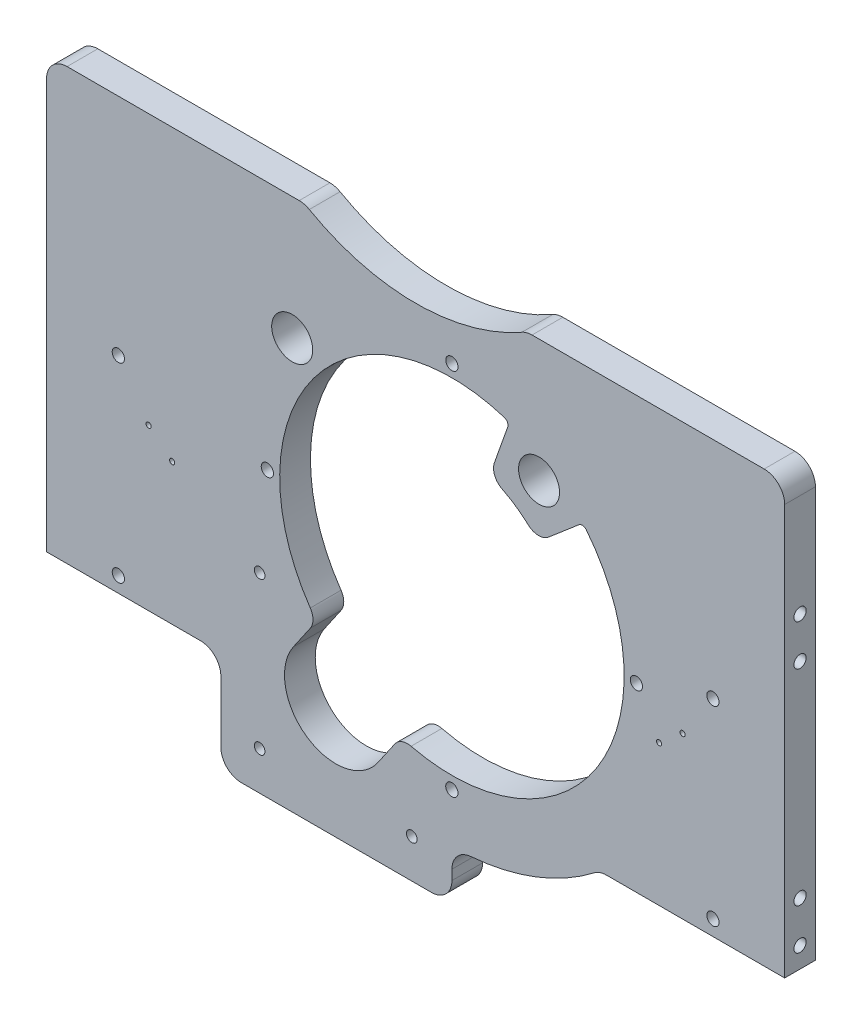
SolidWorks part; units mm, degrees
material "6061 Alloy"
ref_plane "Front Plane" through (0, 0, 0) normal (0, 0, 1) x (1, 0, 0)
ref_plane "Top Plane" through (0, 0, 0) normal (0, 1, 0) x (1, 0, 0)
ref_plane "Right Plane" through (0, 0, 0) normal (1, 0, 0) x (0, 0, -1)
sketch "LayoutSke"
sketch_block_instance "Gearing 2.0-1"
sketch_block "Gearing 2.0" parameters "D5"=76.2, "D6"=25.4, "D7"=101.6, "D8"=19.05, "D1"=228.6, "D2"=123.2, "D3"=85.227, "D4"=76.454, "D9"=39.0329, "D10"=76.454, "D11"=47.625, "D12"=63.5
sketch "Sketch2" plane through (0, 0, 0) normal (0, 0, 1) x (1, 0, 0)
  line L1 (-114.3, 123.2) -> (114.3, 123.2)
  line L2 (-114.3, 123.2) -> (-114.3, -41.9)
  line L3 (-114.3, -41.9) -> (114.3, -41.9)
  line L4 (114.3, 123.2) -> (114.3, -41.9)
  dimension "D1" = 165.1
extrude "Boss-Extrude1" add sketch "Sketch2" along normal blind 9.525
hole_wizard "1/2 (0.5) Diameter Hole1" positions "Sketch3" profile "Sketch4" hole size "1/2" standard "ANSI Inch" end condition through all
sketch "Sketch3" plane through (0, 0, 9.525) normal (0, 0, 1) x (1, 0, 0)
  point P0 (-38.227, 85.227)
  point P3 (38.227, 85.227)
sketch "Sketch4" plane through (-38.227, 85.227, 9.525) normal (1, 0, 0) x (0, -1, 0)
  line L0 (0, 0) -> (0, 9.525)
  line L1 (0, 9.525) -> (6.35, 9.525)
  line L2 (6.35, 9.525) -> (6.35, 0)
  line L5 (6.35, 0) -> (0, 0)
  line L11 (0, -6.35) -> (0, 107.95) construction
  dimension "Thru Hole Dia." = 12.7
  dimension "Thru Hole Depth" = 9.525
ref_axis "MotorShaft" through (-24.7438, -6.3341, 0) along (0, 0, 1)
ref_axis "IntermediateShaft" through (11.2395, 45.9865, 0) along (0, 0, 1)
sketch "Sketch5" plane through (0, 0, 9.525) normal (0, 0, 1) x (1, 0, 0)
  line L0 (11.2395, 45.9865) -> (38.227, 85.227) construction
  line L10 (29.0606, 96.2614) -> (22.9081, 78.9046)
  line L11 (37.8038, 68.6601) -> (51.8105, 80.6153)
  line L12 (11.2395, 45.9865) -> (11.2395, -7.3535) construction
  arc A2 (29.0606, 96.2614) -> (51.8105, 80.6153) centre (11.2395, 45.9865) ccw
  circle A3 centre (11.2395, 45.9865) radius 50.8 construction
  arc A5 (37.8038, 68.6601) -> (22.9081, 78.9046) centre (11.2395, 45.9865) ccw
  dimension "D1" = 2.54
  dimension "D2" = 69.85
  dimension "D3" = 15
  dimension "D4" = 15
extrude "Cut-Extrude2" cut sketch "Sketch5" against normal through all
sketch "Sketch6" plane through (0, 0, 0) normal (0, 0, -1) x (-1, 0, 0)
  line L0 (13.2292, 10.4085) -> (24.7438, -6.3341) construction
  line L1 (26.3093, 19.4043) -> (37.824, 2.6617)
  line L2 (0.149, 1.4126) -> (11.6637, -15.33)
  arc A0 (26.3093, 19.4043) -> (0.149, 1.4126) centre (13.2292, 10.4085) ccw
  arc A1 (11.6637, -15.33) -> (37.824, 2.6617) centre (24.7438, -6.3341) ccw
  arc A2 (-51.8105, 80.6153) -> (-29.0606, 96.2614) centre (-11.2395, 45.9865) ccw construction
  point P4 (18.9865, 2.0372)
  dimension "D1" = 31.75
extrude "Cut-Extrude3" cut sketch "Sketch6" against normal through all
sketch "Sketch7" plane through (0, 0, 0) normal (0, 0, -1) x (-1, 0, 0)
  line L0 (-114.3, 123.2) -> (114.3, 123.2) construction
  line L1 (38.227, 85.227) -> (-38.227, 85.227) construction
  circle A0 centre (0, 180.35) radius 66.675
  point P4 (0, 123.2)
  point P6 (0, 113.675)
  dimension "D1" = 133.35
  dimension "D2" = 9.525
  dimension "D3" = 95.123
extrude "Cut-Extrude4" cut sketch "Sketch7" against normal through all
sketch "Sketch8" plane through (0, 0, 9.525) normal (0, 0, 1) x (1, 0, 0)
  line L0 (114.3, -41.9) -> (114.3, -10.15)
  line L1 (114.3, -41.9) -> (114.3, 123.2) construction
  line L2 (114.3, -10.15) -> (56.9451, -10.15)
  line L3 (114.3, -41.9) -> (11.2395, -41.9)
  line L5 (-114.3, -41.9) -> (114.3, -41.9) construction
  line L6 (11.2395, -41.9) -> (11.2395, -26.4035)
  line L13 (114.3, 123.2) -> (34.3429, 123.2) construction
  line L14 (-114.3, 123.2) -> (-114.3, -41.9) construction
  line L15 (-114.3, -41.9) -> (-60.325, -41.9)
  line L16 (-114.3, -41.9) -> (-114.3, -10.15)
  line L17 (-114.3, -10.15) -> (-60.325, -10.15)
  line L18 (-60.325, -41.9) -> (-60.325, -10.15)
  arc A1 (-4.5366, -4.9671) -> (51.8105, 80.6153) centre (11.2395, 45.9865) ccw construction
  arc A12 (11.2395, -26.4035) -> (56.9451, -10.15) centre (11.2395, 45.9865) ccw
  dimension "D1" = 133.35
  dimension "D2" = 19.05
  dimension "D5" = 53.975
extrude "Cut-Extrude5" cut sketch "Sketch8" against normal through all
sketch "Sketch9" plane through (0, 0, 9.525) normal (0, 0, 1) x (1, 0, 0)
  line L0 (101.6, 54.9375) -> (76.2, 54.9375) construction
  line L1 (114.3, -10.15) -> (114.3, 123.2) construction
  line L2 (114.3, 123.2) -> (34.3429, 123.2) construction
  dimension "D1" = 12.7
  dimension "D2" = 25.4
  dimension "D3" = 68.2625
sketch "Sketch12" plane through (0, 0, 9.525) normal (0, 0, 1) x (1, 0, 0)
  line L0 (114.3, 93.0375) -> (-114.3, 93.0375) construction
  line L1 (-104.775, 113.675) -> (104.775, 113.675) construction
  line L2 (-104.775, 113.675) -> (-104.775, 72.4) construction
  line L3 (-104.775, 72.4) -> (104.775, 72.4) construction
  line L4 (104.775, 113.675) -> (104.775, 72.4) construction
  line L5 (114.3, -10.15) -> (114.3, 123.2) construction
  line L6 (-114.3, 123.2) -> (-114.3, -10.15) construction
  line L7 (114.3, 123.2) -> (114.3, 62.875) construction
  line L8 (114.3, 123.2) -> (34.3429, 123.2) construction
  point P4 (0, 72.4)
  point P5 (-104.775, 93.0375)
  dimension "D1" = 60.325
  dimension "D2" = 9.525
  dimension "D3" = 9.525
fillet "Fillet1" radius 4.7625 4 edges at (22.9081, 78.9046, 4.7625) (37.8038, 68.6601, 4.7625) (-30.697, 13.0246, 4.7625) (-4.5366, -4.9671, 4.7625)
fillet "Fillet5" radius 6.35 9 edges at (-114.3, 123.2, 4.7625) (114.3, 123.2, 4.7625) (34.3429, 123.2, 4.7625) (-34.3429, 123.2, 4.7625) (56.9451, -10.15, 4.7625) (11.2395, -26.4035, 4.7625) (11.2395, -41.9, 4.7625) (-60.325, -41.9, 4.7625) (-60.325, -10.15, 4.7625)
hole_wizard "#10-24 Tapped Hole1" positions "Sketch15" profile "Sketch16" tap size "#10-24" standard "ANSI Inch"
sketch "Sketch15" plane through (-114.3, 0, 0) normal (-1, 0, 0) x (0, 0, 1)
  line L0 (4.7625, 123.2) -> (4.7625, 85.1) construction
  line L1 (0, 123.2) -> (9.525, 123.2) construction
  line L2 (4.7625, 85.1) -> (4.7625, 72.4) construction
  line L3 (4.7625, 72.4) -> (4.7625, 8.9) construction
  line L4 (4.7625, 8.9) -> (4.7625, -3.8) construction
  point P0 (4.7625, 85.1)
  point P2 (4.7625, 72.4)
  point P4 (4.7625, 8.9)
  point P6 (4.7625, -3.8)
  dimension "D1" = 12.7
  dimension "D2" = 63.5
  dimension "D3" = 12.7
  dimension "D4" = 38.1
sketch "Sketch16" plane through (-114.3, 85.1, 4.7625) normal (0, 1, 0) x (0, 0, 1)
  line L0 (0, 0) -> (0, 16.0887)
  line L1 (0, 16.0887) -> (1.8986, 14.9479)
  line L2 (1.8986, 14.9479) -> (1.8986, 0)
  line L5 (1.8986, 0) -> (0, 0)
  line L10 (0, 16.0887) -> (-1.8986, 14.9479) construction
  line L11 (0, -6.35) -> (0, 107.95) construction
  dimension "Tap Drill Dia." = 3.7973
  dimension "Tap Drill Depth" = 14.9479
  dimension "Drill Angle" = 118
cosmetic thread "Hole Thread1" parameters "D1"=9.652, "D2"=4.826
cosmetic thread "Hole Thread2" parameters "D1"=9.652, "D2"=4.826
cosmetic thread "Hole Thread3" parameters "D1"=9.652, "D2"=4.826
cosmetic thread "Hole Thread4" parameters "D1"=9.652, "D2"=4.826
mirror "Mirror2" about plane through (0, 0, 0) normal (1, 0, 0) of "#10-24 Tapped Hole1"
fillet "Fillet6" radius 1.5875 2 edges at (51.8105, 80.6153, 4.7625) (29.0606, 96.2614, 4.7625)
hole_wizard "M2x0.4 Tapped Hole1" positions "Sketch17" profile "Sketch18" tap size "M2x0.4" standard "ANSI Metric" end condition through all
sketch "Sketch17" plane through (0, 0, 0) normal (0, 0, -1) x (-1, 0, 0)
  line L0 (-82.6827, 39.6364) -> (-75.4053, 33.5299) construction
  line L1 (75.4053, 33.5299) -> (82.6827, 39.6364) construction
  line L14 (38.227, 85.227) -> (79.044, 85.227) construction
  line L15 (79.044, 85.227) -> (79.044, 36.5832) construction
  line L17 (-38.227, 85.227) -> (-79.044, 85.227) construction
  line L18 (-79.044, 85.227) -> (-79.044, 36.5832) construction
  line L20 (38.227, 85.227) -> (79.044, 36.5832) construction
  line L22 (-38.227, 85.227) -> (-79.044, 36.5832) construction
  point P0 (-75.4053, 33.5299)
  point P2 (-82.6827, 39.6364)
  point P16 (75.4053, 33.5299)
  point P18 (82.6827, 39.6364)
  dimension "D1" = 63.5
  dimension "D5" = 50
  dimension "D3" = 9.5
  dimension "D4" = 9.5
  dimension "D6" = 50
cosmetic thread "Hole Thread5" parameters "D2"=2
cosmetic thread "Hole Thread6" parameters "D2"=2
sketch "Sketch18" plane through (75.4053, 33.5299, 0) normal (1, 0, 0) x (0, 1, 0)
  line L0 (0, 0) -> (0, 9.525)
  line L1 (0, 9.525) -> (0.8, 9.525)
  line L2 (0.8, 9.525) -> (0.8, 0)
  line L5 (0.8, 0) -> (0, 0)
  line L11 (0, -6.35) -> (0, 107.95) construction
  dimension "Thru Tap Drill Dia." = 1.6
  dimension "Thru Tap Drill Depth" = 9.525
cosmetic thread "Hole Thread10" parameters "D2"=2
cosmetic thread "Hole Thread11" parameters "D2"=2
hole_wizard "M4x0.7 Tapped Hole1" positions "Sketch19" profile "Sketch20" tap size "M4x0.7" standard "ANSI Metric" end condition through all
sketch "Sketch19" plane through (0, 0, 9.525) normal (0, 0, 1) x (1, 0, 0)
  point P0 (-48.3138, 17.2359)
  point P2 (-48.3138, -29.9041)
  point P4 (-1.1738, -29.9041)
sketch "Sketch20" plane through (-48.3138, 17.2359, 9.525) normal (1, 0, 0) x (0, -1, 0)
  line L0 (0, 0) -> (0, 9.525)
  line L1 (0, 9.525) -> (1.65, 9.525)
  line L2 (1.65, 9.525) -> (1.65, 0)
  line L5 (1.65, 0) -> (0, 0)
  line L11 (0, -6.35) -> (0, 107.95) construction
  dimension "Thru Tap Drill Dia." = 3.3
  dimension "Thru Tap Drill Depth" = 9.525
cosmetic thread "Hole Thread7" parameters "D2"=4
cosmetic thread "Hole Thread8" parameters "D2"=4
cosmetic thread "Hole Thread9" parameters "D2"=4
hole_wizard "#10-24 Tapped Hole2" positions "Sketch21" profile "Sketch22" tap size "#10-24" standard "ANSI Inch" end condition through all
sketch "Sketch21" plane through (0, 0, 9.525) normal (0, 0, 1) x (1, 0, 0)
  line L0 (114.3, -10.15) -> (114.3, 116.85) construction
  line L1 (114.3, -10.15) -> (59.1501, -10.15) construction
  line L2 (0, 0) -> (0, 32.4793) construction
  line L4 (107.95, 123.2) -> (36.0611, 123.2) construction
  point P0 (-45.9257, 45.9967)
  point P2 (11.2395, 103.1365)
  point P4 (68.3793, 45.9713)
  point P6 (11.2141, -11.1685)
  point P8 (92.075, 53.6675)
  point P10 (92.075, -5.3875)
  point P12 (-92.075, -5.3875)
  point P14 (-92.075, 53.6675)
  point P27 (0, 0)
  point P30 (0, 0)
  point P31 (0, 0)
  dimension "D1" = 22.225
  dimension "D2" = 4.7625
  dimension "D3" = 69.5325
sketch "Sketch22" plane through (-45.9257, 45.9967, 9.525) normal (1, 0, 0) x (0, -1, 0)
  line L0 (0, 0) -> (0, 9.525)
  line L1 (0, 9.525) -> (1.8986, 9.525)
  line L2 (1.8986, 9.525) -> (1.8986, 0)
  line L5 (1.8986, 0) -> (0, 0)
  line L11 (0, -6.35) -> (0, 107.95) construction
  dimension "Thru Tap Drill Dia." = 3.7973
  dimension "Thru Tap Drill Depth" = 9.525
cosmetic thread "Hole Thread12" parameters "D2"=4.826
cosmetic thread "Hole Thread13" parameters "D2"=4.826
cosmetic thread "Hole Thread14" parameters "D2"=4.826
cosmetic thread "Hole Thread15" parameters "D2"=4.826
cosmetic thread "Hole Thread16" parameters "D2"=4.826
cosmetic thread "Hole Thread17" parameters "D2"=4.826
cosmetic thread "Hole Thread18" parameters "D2"=4.826
cosmetic thread "Hole Thread19" parameters "D2"=4.826
